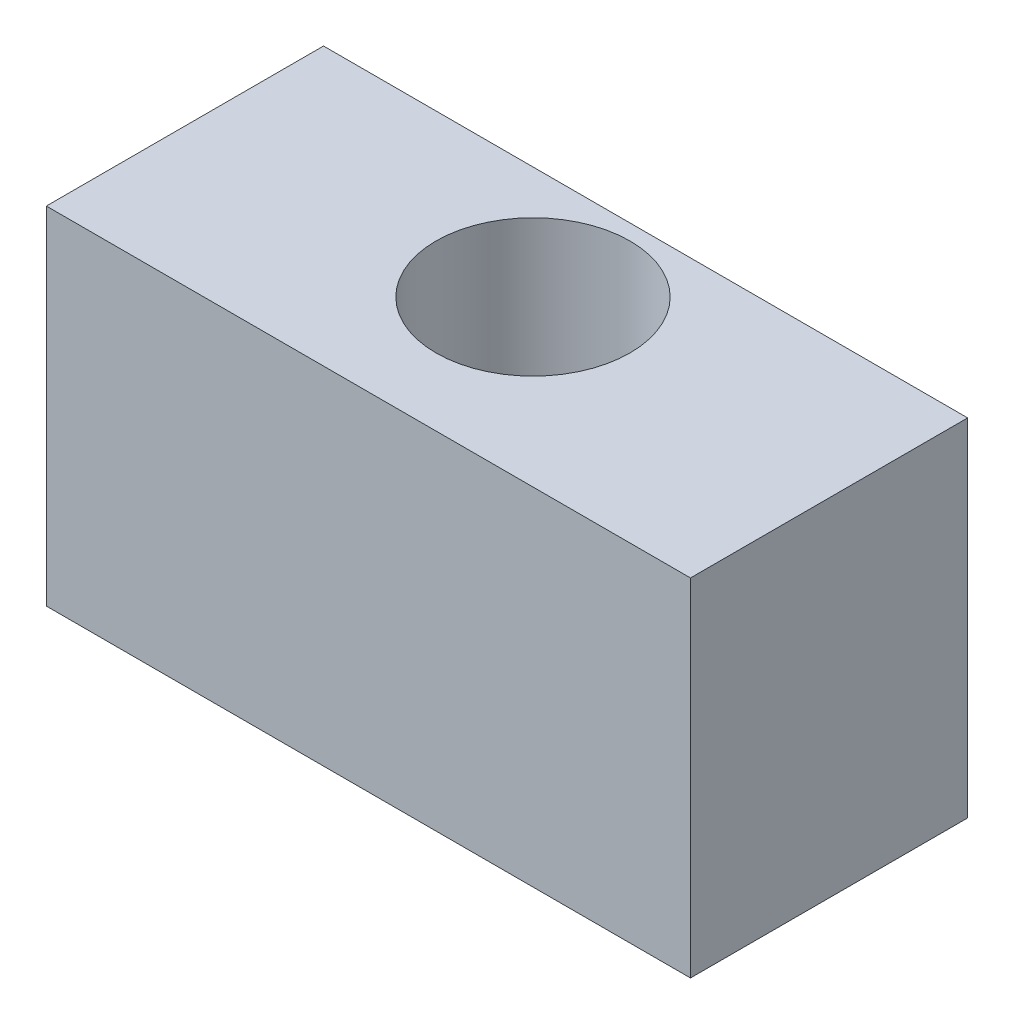
SolidWorks part; units mm, degrees
material "Polyethylene Cross-Linked"
ref_plane "Front Plane" through (0, 0, 0) normal (0, 0, 1) x (1, 0, 0)
ref_plane "Top Plane" through (0, 0, 0) normal (0, 1, 0) x (1, 0, 0)
ref_plane "Right Plane" through (0, 0, 0) normal (1, 0, 0) x (0, 0, -1)
sketch "Sketch1" plane through (0, 0, 0) normal (0, 1, 0) x (1, 0, 0)
  line L1 (0, 0) -> (29.5139, 0)
  line L2 (0, 0) -> (0, 12.7)
  line L3 (0, 12.7) -> (29.5139, 12.7)
  line L4 (29.5139, 0) -> (29.5139, 12.7)
  circle A0 centre (14.7569, 7.5406) radius 4.445
extrude "Boss-Extrude1" add sketch "Sketch1" along normal blind 15.875
sketch "Sketch3" plane through (0, 15.875, 0) normal (0, 1, 0) x (1, 0, 0)
